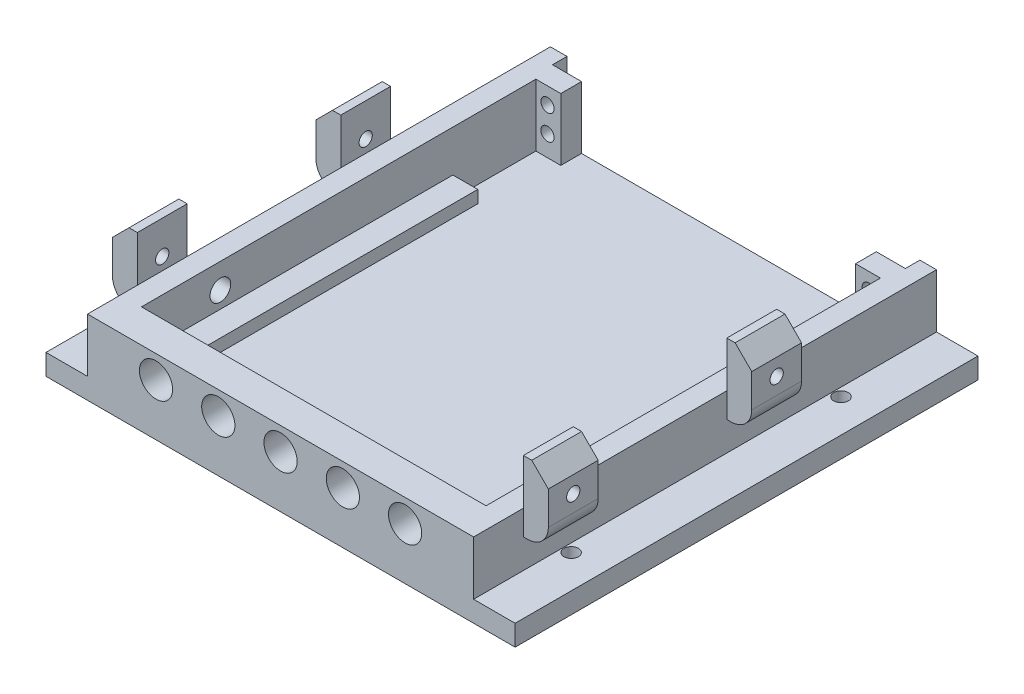
SolidWorks part; units mm, degrees
ref_plane "Alzado" through (0, 0, 0) normal (0, 0, 1) x (1, 0, 0)
ref_plane "Planta" through (0, 0, 0) normal (0, 1, 0) x (1, 0, 0)
ref_plane "Vista lateral" through (0, 0, 0) normal (1, 0, 0) x (0, 0, -1)
sketch "Croquis1" plane through (0, 0, 0) normal (0, 1, 0) x (1, 0, 0)
  line L1 (-46.5, 54) -> (46.5, 54)
  line L2 (-46.5, 54) -> (-46.5, -54)
  line L3 (-46.5, -54) -> (46.5, -54)
  line L4 (46.5, 54) -> (46.5, -54)
  line L5 (-46.5, 54) -> (46.5, -54) construction
  line L6 (-46.5, -54) -> (46.5, 54) construction
  point P0 (0, 0)
  dimension "D1" = 108
  dimension "D2" = 93
extrude "Saliente-Extruir1" add sketch "Croquis1" along normal blind 3
sketch "Croquis2" plane through (0, 3, 0) normal (0, 1, 0) x (1, 0, 0)
  line L1 (-46.5, 54) -> (-41.5, 54)
  line L2 (-46.5, 54) -> (-46.5, -54)
  line L4 (-41.5, 54) -> (-41.5, -46)
  line L5 (46.5, 54) -> (-46.5, 54) construction
  line L7 (46.5, -54) -> (46.5, 54)
  line L8 (46.5, 54) -> (41.5, 54)
  line L9 (41.5, -46) -> (41.5, 54)
  line L10 (-46.5, -54) -> (46.5, -54)
  line L12 (-41.5, -46) -> (41.5, -46)
  dimension "D1" = 5
  dimension "D2" = 5
  dimension "D3" = 100
  dimension "D4" = 100
extrude "Saliente-Extruir2" add sketch "Croquis2" along normal blind 15
ref_plane "Plano1" through (0, 0, -48) normal (0, 0, -1) x (-1, 0, 0)
sketch "Croquis10" plane through (46.5, 0, 0) normal (1, 0, 0) x (0, 0, -1)
  line L0 (13, 29) -> (13, 12) construction
  line L5 (-33, 18) -> (10, 18) construction
  line L10 (51.15, 0) -> (-51.15, 0) construction
  line L15 (10, 12) -> (19, 12)
  line L16 (10, 12) -> (10, 29)
  line L17 (10, 29) -> (19, 29)
  line L18 (19, 12) -> (19, 29)
  line L19 (-36, 12) -> (-30, 12)
  line L20 (13, 12) -> (7, 12)
  line L22 (13, 29) -> (7, 29)
  line L23 (7, 12) -> (7, 29)
  line L24 (-33, 12) -> (-42, 12)
  line L25 (-11.5, 11.4546) -> (-11.5, 24.5454)
  line L26 (54, 18) -> (54, 0) construction
  line L27 (-54, 18) -> (-54, 0) construction
  line L28 (-54, 0) -> (54, 0) construction
  line L29 (-42, 12) -> (-42, 29)
  line L30 (-36, 29) -> (-30, 29)
  line L31 (-33, 29) -> (-42, 29)
  line L32 (-30, 12) -> (-30, 29)
  circle A1 centre (13, 21) radius 1.6
  circle A2 centre (-36, 21) radius 1.6
  point P25 (-11.5, 18)
  line M7 (54, 18) -> (-54, 18)
  dimension "D10" = 3.2
  dimension "D8" = 9
  dimension "D4" = 8
  dimension "D2" = 12
  dimension "D3" = 35
  dimension "D5" = 12
  dimension "D6" = 21
  dimension "D7" = 18
  dimension "D14" = 3
  dimension "D15" = 6
extrude "Saliente-Extruir4" add sketch "Croquis10" along normal blind 6 contours L18 L17 L16 A1 M7 | L15 L18 L16 M7 | L23 L20 L16 M7 | L23 L16 L22 M7 | L32 L30 L31 L29 A2 M7 | L19 L32 L29 L24 M7 region at (46.5, 15, -14.5) region at (46.5, 15, -8.5) region at (46.5, 15, 36) region at (46.5, 23.6622, 36) region at (46.5, 23.5, -8.5) region at (46.5, 23.7211, -14.6326)
fillet "Redondeo1" radius 5 2 edges at (52.5, 12, -13) (52.5, 12, 36)
mirror "Simetría1" about plane through (0, 0, 0) normal (1, 0, 0) of "Saliente-Extruir4", "Redondeo1"
sketch "Croquis12" plane through (-41.5, 0, 0) normal (1, 0, 0) x (0, 0, -1)
  line L0 (-46, 18) -> (54, 18) construction
  line L1 (49, 18) -> (54, 18)
  line L2 (49, 18) -> (49, 3)
  line L3 (49, 3) -> (54, 3)
  line L4 (54, 18) -> (54, 3)
  dimension "D1" = 5
extrude "Saliente-Extruir5" add sketch "Croquis12" along normal blind 6
mirror "Simetría2" about plane through (0, 0, 0) normal (1, 0, 0) of "Saliente-Extruir5"
sketch "Croquis13" plane through (0, 0, 54) normal (0, 0, 1) x (1, 0, 0)
  line L0 (-46.5, 0) -> (46.5, 0) construction
  line L2 (0, 12.5) -> (20, 12.5) construction
  line L3 (0, 12.5) -> (-20, 12.5) construction
  line L4 (0, 0) -> (0, 12.5) construction
  circle A0 centre (-20, 12.5) radius 4
  circle A1 centre (0, 12.5) radius 4
  circle A2 centre (20, 12.5) radius 4
  dimension "D1" = 8
  dimension "D2" = 8
  dimension "D3" = 8
  dimension "D4" = 12.5
  dimension "D5" = 20
  dimension "D6" = 20
sketch "Croquis14" plane through (0, 0, -54) normal (0, 0, -1) x (-1, 0, 0)
  line L0 (38.7, 14) -> (38.7, 8) construction
  line L2 (35.5, 18) -> (46.5, 18) construction
  line L3 (35.5, 3) -> (35.5, 18) construction
  circle A0 centre (38.7, 14) radius 1.6
  circle A1 centre (38.7, 8) radius 1.6
  dimension "D1" = 3.2
  dimension "D2" = 3.2
  dimension "D3" = 6
  dimension "D4" = 4
  dimension "D5" = 3.2
extrude "Cortar-Extruir2" cut sketch "Croquis14" against normal up to next
mirror "Simetría3" about plane through (0, 0, 0) normal (1, 0, 0) of "Cortar-Extruir2"
sketch "Croquis15" plane through (0, 0, -54) normal (0, 0, -1) x (-1, 0, 0)
  line L0 (-38.7, 14) -> (38.7, 14) construction
sketch "Croquis16" plane through (-46.5, 0, 0) normal (-1, 0, 0) x (0, 0, 1)
  line L0 (0, 0) -> (0, 12) construction
  line L1 (-54, 0) -> (54, 0) construction
  line L3 (0, 12) -> (27, 12) construction
  circle A0 centre (27, 12) radius 2.5
  dimension "D1" = 5
  dimension "D2" = 12
  dimension "D3" = 27
extrude "Cortar-Extruir3" cut sketch "Croquis16" against normal blind 93
sketch "Croquis17" plane through (0, 0, 0) normal (0, 1, 0) x (1, 0, 0)
  line L6 (46.5, 54) -> (42.5, 54)
  line L7 (46.5, 54) -> (46.5, 57.5)
  line L8 (46.5, 57.5) -> (42.5, 57.5)
  line L9 (42.5, 54) -> (42.5, 57.5)
  dimension "D1" = 3.5
  dimension "D2" = 4
extrude "Saliente-Extruir6" add sketch "Croquis17" along normal up to surface (18 mm away) up to face at (0, 18, -6)
mirror "Simetría4" about plane through (0, 0, 0) normal (1, 0, 0) of "Saliente-Extruir6"
chamfer "Chaflán2" distance 4 angle 45 4 edges at (52.5, 29, -13) (52.5, 29, 36) (-52.5, 29, -13) (-52.5, 29, 36)
sketch "Croquis18" plane through (46.5, 0, 0) normal (1, 0, 0) x (0, 0, -1)
  line L5 (57.5, 18) -> (57.5, 0) construction
  line L6 (-54, 0) -> (57.5, 0)
  line L7 (-54, 0) -> (-54, 5)
  line L8 (-54, 5) -> (57.5, 5)
  line L9 (57.5, 0) -> (57.5, 5)
  dimension "D1" = 5
extrude "Saliente-Extruir7" add sketch "Croquis18" along normal blind 10
sketch "Croquis20" plane through (-41.5, 0, 0) normal (1, 0, 0) x (0, 0, -1)
  line L0 (-46, 18) -> (-46, 3) construction
  line L1 (-46, 8) -> (29, 8)
  line L2 (-46, 8) -> (-46, 5)
  line L3 (-46, 5) -> (29, 5)
  line L4 (29, 8) -> (29, 5)
  line L5 (-46, 3) -> (49, 3) construction
  dimension "D1" = 3
  dimension "D2" = 75
  dimension "D3" = 2
extrude "Saliente-Extruir8" add sketch "Croquis20" along normal blind 6
mirror "Simetría9" about plane through (0, 0, 0) normal (1, 0, 0) of "Saliente-Extruir8"
sketch "Croquis21" plane through (46.5, 0, 0) normal (-1, 0, 0) x (0, 0, 1)
  circle A1 centre (36, 21) radius 1.6
sketch "Croquis22" plane through (-46.5, 0, 0) normal (1, 0, 0) x (0, 0, -1)
  circle A0 centre (13, 21) radius 1.6
sketch "Croquis24" plane through (0, 5, 0) normal (0, 1, 0) x (1, 0, 0)
  line L0 (56.5, 57.5) -> (56.5, -54) construction
  line L1 (56.5, 57.5) -> (46.5, 57.5) construction
  circle A0 centre (48.5, 32.5) radius 1.75
  dimension "D1" = 3.5
  dimension "D2" = 8
  dimension "D3" = 25
extrude "Cortar-Extruir4" cut sketch "Croquis24" against normal up to next
mirror "Simetría11" about plane through (0, 0, 0) normal (0, 0, 1) of "Cortar-Extruir4"
mirror "Simetría12" about plane through (0, 0, 0) normal (1, 0, 0) of "Simetría11", "Saliente-Extruir7", "Cortar-Extruir4"
sketch "Croquis28" plane through (0, 0, -54) normal (0, 0, -1) x (-1, 0, 0)
  circle A0 centre (-38.7, 14) radius 1.6
sketch "Croquis29" plane through (0, 0, 0) normal (0, -1, 0) x (1, 0, 0)
  line L0 (-56.5, 54) -> (56.5, 54) construction
  line L1 (-41.5, 39) -> (41.5, 39)
  line L2 (-41.5, 39) -> (-41.5, -34)
  line L3 (-41.5, -34) -> (41.5, -34)
  line L4 (41.5, 39) -> (41.5, -34)
  line L5 (-56.5, 54) -> (-56.5, -57.5) construction
  line L6 (56.5, 54) -> (56.5, -57.5) construction
  line L7 (42.5, -54) -> (-42.5, -54) construction
  line L8 (-26.4569, 33.1211) -> (-36.5, 23.078)
  line L9 (-26.4569, 33.1211) -> (-23.4758, 30)
  line L10 (-23.4758, 30) -> (-33.5406, 20.3869)
  line L11 (-33.5406, 20.3869) -> (-36.5, 23.078)
  line L12 (-41.5, 39) -> (41.5, -34) construction
  dimension "D1" = 15
  dimension "D2" = 15
  dimension "D3" = 15
  dimension "D4" = 20
  dimension "D5" = 45
  dimension "D6" = 4
  dimension "D7" = 5
  dimension "D8" = 9
sketch "Croquis30" plane through (0, 0, 0) normal (0, -1, 0) x (1, 0, 0)
  line L0 (-56.5, 54) -> (56.5, -57.5)
sketch "Croquis31" plane through (0, 0, 54) normal (0, 0, 1) x (1, 0, 0)
  line L1 (0, -15.95) -> (0, 15.95) construction
  line L2 (-56.5, 0) -> (56.5, 0) construction
  line L4 (0, 0) -> (0, 12.5) construction
  circle A0 centre (-30, 12.5) radius 4
  circle A1 centre (30, 12.5) radius 4
  circle A2 centre (-15, 12.5) radius 4
  circle A3 centre (0, 12.5) radius 4 construction
  circle A4 centre (0, 12.5) radius 4
  circle A5 centre (15, 12.5) radius 4
  point P14 (0, 14.0014)
  point P16 (0, 0)
  point P17 (0, 14.0014)
  point P20 (0, 0)
  dimension "D1" = 8
  dimension "D3" = 8
  dimension "D5" = 8
  dimension "D7" = 12.5
  dimension "D8" = 30
  dimension "D9" = 8
  dimension "D2" = 15
  dimension "D4" = 12.5
  dimension "D6" = 12.5
  dimension "D10" = 12.5
extrude "Cortar-Extruir10" cut sketch "Croquis31" against normal up to next
